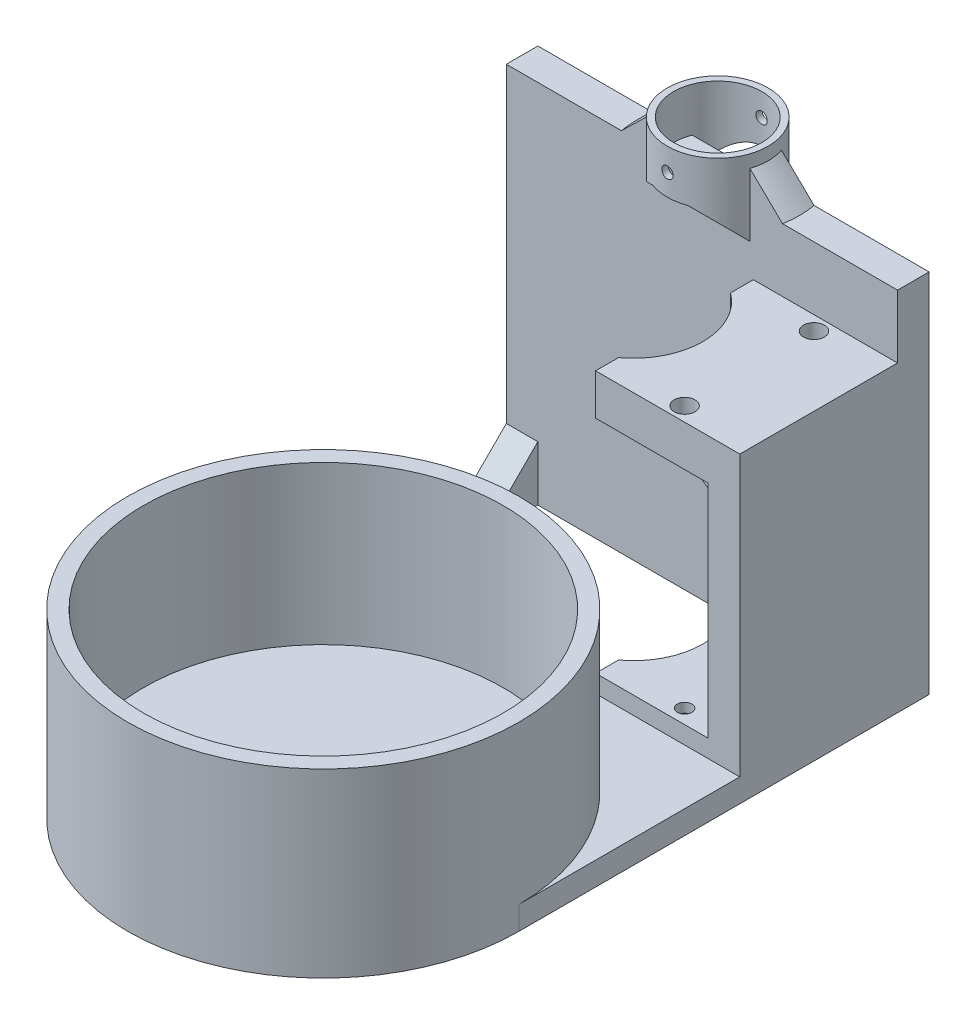
SolidWorks part; units mm, degrees
ref_plane "Front Plane" through (0, 0, 0) normal (0, 0, 1) x (1, 0, 0)
ref_plane "Top Plane" through (0, 0, 0) normal (0, 1, 0) x (1, 0, 0)
ref_plane "Right Plane" through (0, 0, 0) normal (1, 0, 0) x (0, 0, -1)
sketch "Sketch1" plane through (0, 0, 0) normal (0, 0, 1) x (1, 0, 0)
  line L1 (-31, 24) -> (31, 24)
  line L2 (-31, 24) -> (-31, -24)
  line L3 (-31, -24) -> (31, -24)
  line L4 (31, 24) -> (31, -24)
  line L5 (0, -24) -> (0, 24) construction
  line L6 (-31, 0) -> (31, 0) construction
  point P0 (0, 0)
  dimension "D1" = 62
  dimension "D2" = 48
extrude "Boss-Extrude1" add sketch "Sketch1" along normal blind 5
sketch "Sketch2" plane through (0, 0, 5) normal (0, 0, 1) x (1, 0, 0)
  line L0 (31, -24) -> (31, 24) construction
  circle A0 centre (6, 0) radius 9.6
  circle A1 centre (6, 7) radius 1.65
  circle A3 centre (13, 0) radius 1.65
  circle A4 centre (6, -7) radius 1.65
  circle A5 centre (-1, 0) radius 1.65
  point P4 (6.607, -1.5824)
  point P8 (-4, 0)
  point P16 (6, 0)
  dimension "D1" = 19.2
  dimension "D2" = 25
  dimension "D3" = 7
  dimension "D4" = 3.3
  dimension "D5" = 4
extrude "Cut-Extrude2" cut sketch "Sketch2" against normal blind 5 contours A1 | A3 | A4 | A5 region at (6, 7, 5) region at (13, 0, 5) region at (6, -7, 5) region at (-1, 0, 5)
sketch "Sketch3" plane through (0, 0, 0) normal (0, 0, -1) x (-1, 0, 0)
  circle A1 centre (1, 0) radius 1.65
  circle A2 centre (1, 0) radius 1.65
  circle A3 centre (-6, -7) radius 1.65
  circle A4 centre (-6, -7) radius 1.65
  circle A5 centre (-13, 0) radius 1.65
  circle A6 centre (-13, 0) radius 1.65
  circle A7 centre (-6, 7) radius 1.65
  circle A8 centre (-6, 7) radius 1.65
  circle A9 centre (-6, 0) radius 9.6
  circle A10 centre (-6, 0) radius 9.6 construction
  circle A11 centre (-6, 0) radius 11
  dimension "D6" = 22
  dimension "D1" = 0
  dimension "D2" = 0
  dimension "D3" = 0
  dimension "D4" = 0
  dimension "D5" = 0
extrude "Boss-Extrude2" add sketch "Sketch3" along normal blind 2
sketch "Sketch4" plane through (0, 0, 5) normal (0, 0, 1) x (1, 0, 0)
  circle A0 centre (6, 0) radius 9.6
  circle A1 centre (13, 0) radius 1.65 construction
  circle A2 centre (6, 7) radius 1.65 construction
  circle A3 centre (13, 0) radius 1.65 construction
  circle A4 centre (6, 7) radius 1.65 construction
  point P8 (0, 0)
  point P9 (0, 0)
  dimension "D1" = 19.2
extrude "Cut-Extrude4" cut sketch "Sketch4" against normal blind 5
sketch "Sketch5" plane through (0, 0, 5) normal (0, 0, 1) x (1, 0, 0)
  line L0 (8.15, -24) -> (8.15, -17.5)
  line L1 (-7.85, 17.5) -> (37.15, 17.5) construction
  line L2 (-7.85, 17.5) -> (-7.85, -17.5) construction
  line L3 (-7.85, -17.5) -> (37.15, -17.5) construction
  line L4 (37.15, 17.5) -> (37.15, -17.5)
  line L5 (14.65, -17.5) -> (14.65, 17.5) construction
  line L6 (-7.85, 0) -> (37.15, 0) construction
  line L7 (31, 24) -> (8.15, 24)
  line L8 (31, 24) -> (31, 17.5)
  line L9 (31, 17.5) -> (8.15, 17.5)
  line L10 (8.15, 24) -> (8.15, 17.5)
  line L11 (31, -17.5) -> (8.15, -17.5)
  line L12 (31, -24) -> (31, -17.5)
  line L13 (31, -24) -> (8.15, -24)
  line L14 (31, 17.5) -> (31, -17.5)
  line L15 (26, 17.5) -> (26, -17.5)
  circle A0 centre (13, 0) radius 1.65 construction
  point P0 (14.65, 0)
  line M9 (31, -24) -> (31, 24)
  line M10 (31, 24) -> (-31, 24)
  line M12 (-31, -24) -> (31, -24)
  dimension "D1" = 45
  dimension "D2" = 35
  dimension "D3" = 29
  dimension "D4" = 5
extrude "Boss-Extrude3" add sketch "Sketch5" along normal blind 25 contours L10 L9 M10 M9 | L11 L9 L4 M9 | L11 L0 M9 M12 region at (19.575, -20.75, 5) region at (28.5, 0, 5) region at (19.575, 20.75, 5)
sketch "Sketch6" plane through (0, -17.5, 0) normal (0, 1, 0) x (1, 0, 0)
  line L1 (-0.7, -7.25) -> (20, -7.25) construction
  line L2 (-0.7, -7.25) -> (-0.7, -27.75) construction
  line L3 (-0.7, -27.75) -> (20, -27.75) construction
  line L4 (20, -7.25) -> (20, -27.75) construction
  line L5 (9.65, -27.75) -> (9.65, -7.25) construction
  line L6 (-0.7, -17.5) -> (20, -17.5) construction
  line L7 (26, -30) -> (26, -5) construction
  circle A0 centre (20, -27.75) radius 1.15
  circle A1 centre (20, -7.25) radius 1.15
  circle A2 centre (-0.7, -7.25) radius 1.15
  circle A3 centre (-0.7, -27.75) radius 1.15
  point P0 (9.65, -17.5)
  point P6 (9.65, -17.5666)
  point P11 (26, -17.5)
  dimension "D4" = 2.3
  dimension "D1" = 20.7
  dimension "D2" = 20.5
  dimension "D3" = 6
extrude "Cut-Extrude5" cut sketch "Sketch6" against normal blind 25 and the other way through all
sketch "Sketch7" plane through (0, 24, 0) normal (0, 1, 0) x (1, 0, 0)
  circle A0 centre (0.45, -7.25) radius 1.65
  circle A1 centre (20, -7.25) radius 1.65
  circle A2 centre (20, -27.75) radius 1.65
  circle A3 centre (0.45, -27.75) radius 1.65
  dimension "D1" = 3.3
extrude "Cut-Extrude6" cut sketch "Sketch7" against normal blind 5
mirror "Mirror1" about plane through (0, 0, 0) normal (0, 1, 0) of "Cut-Extrude6"
sketch "Sketch8" plane through (0, 24, 0) normal (0, 1, 0) x (1, 0, 0)
  line L0 (8.15, -30) -> (8.15, -5) construction
  circle A0 centre (1.65, -17.5) radius 11
  point P2 (0, 0)
  point P5 (8.15, -17.5)
  dimension "D1" = 22
  dimension "D2" = 6.5
extrude "Cut-Extrude7" cut sketch "Sketch8" against normal through all
sketch "Sketch9" plane through (0, 24, 0) normal (0, 1, 0) x (1, 0, 0)
  line L1 (8.15, -30) -> (27.15, -30)
  line L2 (8.15, -30) -> (8.15, -90)
  line L3 (8.15, -90) -> (27.15, -90)
  line L4 (27.15, -30) -> (27.15, -90)
  dimension "D1" = 19
  dimension "D2" = 60
extrude "Boss-Extrude4" add sketch "Sketch9" against normal blind 3
sketch "Sketch10" plane through (0, 24, 0) normal (0, 1, 0) x (1, 0, 0)
  line L0 (27.15, -90) -> (27.15, -30) construction
  line L1 (27.15, -35) -> (8.15, -35)
  line L2 (27.15, -35) -> (27.15, -90)
  line L3 (27.15, -90) -> (8.15, -90)
  line L4 (8.15, -35) -> (8.15, -90)
  dimension "D1" = 55
extrude "Boss-Extrude5" add sketch "Sketch10" along normal blind 3.7
sketch "Sketch11" plane through (0, 0, 5) normal (0, 0, 1) x (1, 0, 0)
  line L0 (-31, -24) -> (8.15, -24) construction
  line L1 (-31, 24) -> (-26, 24)
  line L2 (-31, 24) -> (-31, -24)
  line L3 (-31, -24) -> (-26, -24)
  line L4 (-26, 24) -> (-26, -24)
  dimension "D1" = 5
extrude "Boss-Extrude6" add sketch "Sketch11" along normal up to surface (25 mm away) up to face at (20.09, 4.2, 30)
sketch "Sketch12" plane through (0, -24, 0) normal (0, -1, 0) x (1, 0, 0)
  line L0 (-31, 30) -> (31, 30)
  line L1 (31, 30) -> (31, 65)
  line L2 (-31, 65) -> (-31, 30)
  arc A0 (31, 65) -> (-31, 65) centre (0, 65) ccw
  point P7 (31, 65)
  point P8 (-1.3589, 65)
  point P9 (0, 0)
  dimension "D1" = 35
extrude "Boss-Extrude7" add sketch "Sketch12" against normal blind 3.7
sketch "Sketch13" plane through (0, -20.3, 0) normal (0, 1, 0) x (1, 0, 0)
  circle A0 centre (0, -65) radius 31
  arc A1 (-31, -65) -> (31, -65) centre (0, -65) ccw construction
  circle A2 centre (0, -65) radius 28.5
  dimension "D1" = 57
extrude "Boss-Extrude8" add sketch "Sketch13" along normal blind 25
sketch "Sketch14" plane through (0, 24, 0) normal (0, 1, 0) x (1, 0, 0)
  line L0 (31, -30) -> (31, 0) construction
  line L1 (-31, 0) -> (31, 0)
  line L2 (-31, 0) -> (-31, -5)
  line L3 (-31, -5) -> (31, -5)
  line L4 (31, 0) -> (31, -5)
  line L5 (8.15, -5) -> (-26, -5) construction
extrude "Boss-Extrude9" add sketch "Sketch14" along normal blind 10
sketch "Sketch15" plane through (0, 34, 0) normal (0, 1, 0) x (1, 0, 0)
  line L0 (31, -5) -> (31, 0) construction
  circle A0 centre (0, -2.5) radius 8
  circle A1 centre (0, -2.5) radius 7
  point P3 (0, 0)
  point P5 (0, 0)
  point P8 (31, -2.5)
  dimension "D1" = 14
  dimension "D2" = 16
extrude "Boss-Extrude10" add sketch "Sketch15" along normal blind 7
chamfer "Chamfer1" distance 5 angle 45 2 edges at (8, 34, 2.5) (-8, 34, 2.5)
sketch "Sketch16" plane through (0, 0, 0) normal (0, 0, -1) x (-1, 0, 0)
  circle A0 centre (0, 37.4061) radius 0.9
  point P2 (0, 0)
  dimension "D1" = 1.8
extrude "Cut-Extrude8" cut sketch "Sketch16" against normal through all both and the other way through all
chamfer "Chamfer2" distance 5 angle 45 3 edges at (-7.0688, 34, 5) (7.0688, 34, 0) (-28.5, -20.3, 30)
sketch "Sketch17" plane through (0, 27.7, 0) normal (0, 1, 0) x (1, 0, 0)
  line L1 (27.15, -30) -> (8.15, -30)
  line L2 (27.15, -30) -> (27.15, -90)
  line L3 (27.15, -90) -> (8.15, -90)
  line L4 (8.15, -30) -> (8.15, -90)
extrude "Cut-Extrude9" cut sketch "Sketch17" against normal blind 10
sketch "Sketch18" plane through (-31, 0, 0) normal (-1, 0, 0) x (0, 0, 1)
  line L1 (35, -20.3) -> (5, -20.3)
  line L2 (35, -20.3) -> (35, 24)
  line L3 (35, 24) -> (5, 24)
  line L4 (5, -20.3) -> (5, 24)
extrude "Cut-Extrude10" cut sketch "Sketch18" against normal blind 10
chamfer "Chamfer3" distance 5 angle 45 1 edges at (-28.5, -20.3, 5)
